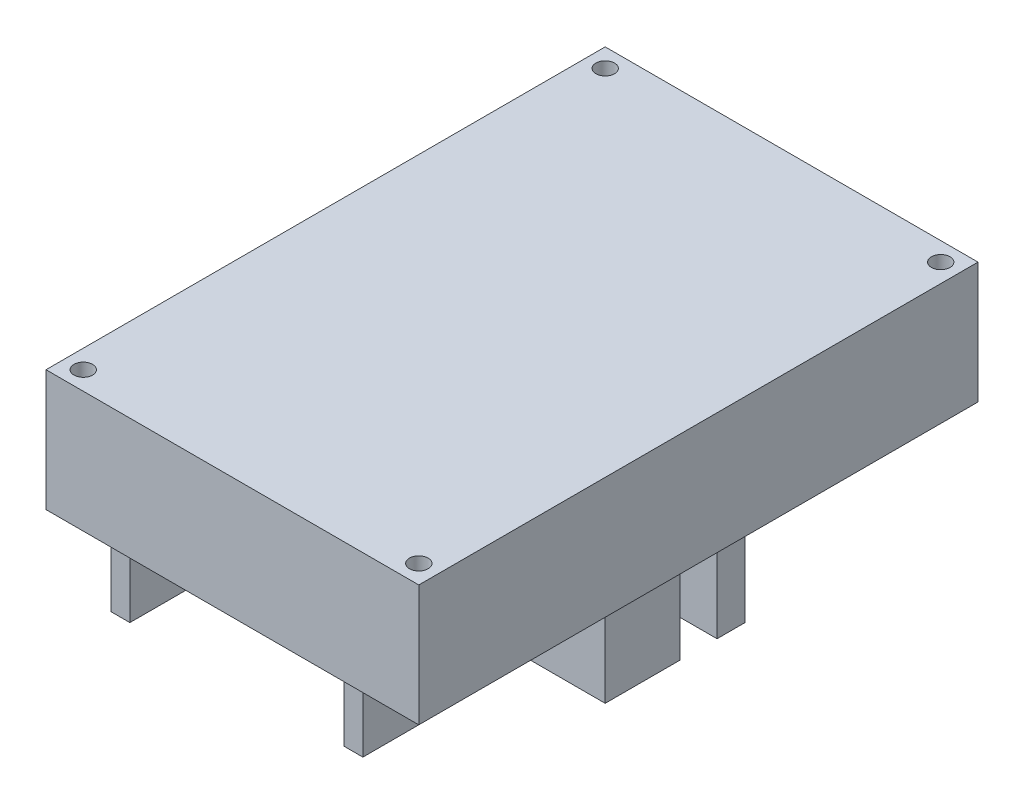
SolidWorks part; units mm, degrees
ref_plane "Plan de face" through (0, 0, 0) normal (0, 0, 1) x (1, 0, 0)
ref_plane "Plan de dessus" through (0, 0, 0) normal (0, 1, 0) x (1, 0, 0)
ref_plane "Plan de droite" through (0, 0, 0) normal (1, 0, 0) x (0, 0, -1)
sketch "Esquisse1" plane through (0, 0, 0) normal (0, 1, 0) x (1, 0, 0)
  line L0 (0, -55) -> (0, 55) construction
  line L1 (-20, -30) -> (20, -30)
  line L2 (-20, -30) -> (-20, 30)
  line L3 (-20, 30) -> (20, 30)
  line L4 (20, -30) -> (20, 30)
  line L5 (-20, -30) -> (20, 30) construction
  line L6 (-20, 30) -> (20, -30) construction
  line L7 (-55, 0) -> (55, 0) construction
  circle A0 centre (-18, 28) radius 1
  circle A1 centre (18, 28) radius 1
  circle A2 centre (18, -28) radius 1
  circle A3 centre (-18, -28) radius 1
  point P0 (0, 0)
  dimension "D5" = 2
  dimension "D1" = 40
  dimension "D2" = 60
  dimension "D3" = 2
  dimension "D4" = 2
extrude "Boss.-Extru.1" add sketch "Esquisse1" along normal mid plane 13
sketch "Esquisse3" plane through (0, -6.5, 0) normal (0, -1, 0) x (1, 0, 0)
  line L0 (-20, 30) -> (20, 30) construction
  line L1 (-17, 26) -> (-15, 26)
  line L2 (-17, 26) -> (-17, -21)
  line L3 (-17, -21) -> (-15, -21)
  line L4 (-15, 26) -> (-15, -21)
  line L5 (8, 26) -> (10, 26)
  line L6 (8, 26) -> (8, -21)
  line L7 (8, -21) -> (10, -21)
  line L8 (10, 26) -> (10, -21)
  line L9 (10, 8) -> (18, 8)
  line L10 (10, 8) -> (10, 0)
  line L11 (10, 0) -> (18, 0)
  line L12 (18, 8) -> (18, 0)
  line L17 (10, -4) -> (18, -4)
  line L18 (10, -4) -> (10, -7)
  line L19 (10, -7) -> (18, -7)
  line L20 (18, -4) -> (18, -7)
  line L21 (20, -30) -> (-20, -30) construction
  line L22 (-20, -30) -> (-20, 30) construction
  line L23 (20, 30) -> (20, -30) construction
  dimension "D1" = 4
  dimension "D2" = 9
  dimension "D3" = 3
  dimension "D4" = 2
  dimension "D5" = 2
  dimension "D6" = 27
  dimension "D7" = 2
  dimension "D8" = 8
  dimension "D9" = 22
  dimension "D10" = 23
  dimension "D11" = 3
  dimension "D12" = 8
extrude "Boss.-Extru.2" add sketch "Esquisse3" along normal blind 10 contours L12 L9 L8 L11 | L20 L17 L8 L19 | L8 L5 L6 L7 | L4 L1 L2 L3 region at (-16, -6.5, 2.5) region at (9, -6.5, 2.5) region at (14, -6.5, 4) region at (14, -6.5, -5.5)
